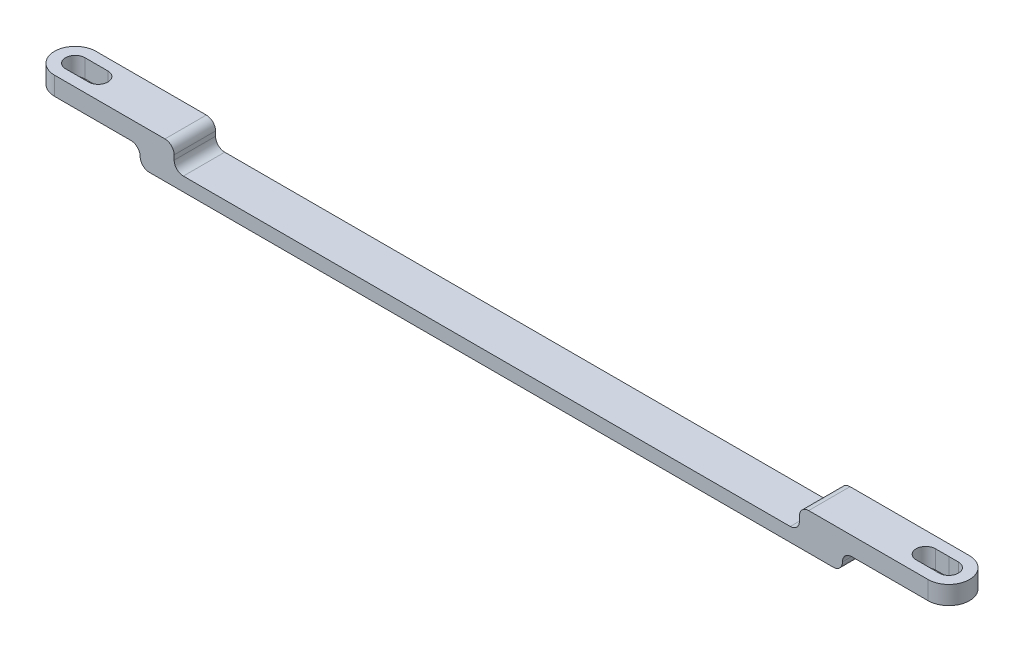
SolidWorks part; units mm, degrees
ref_plane "Front" through (0, 0, 0) normal (0, 0, 1) x (1, 0, 0)
ref_plane "Top" through (0, 0, 0) normal (0, 1, 0) x (1, 0, 0)
ref_plane "Right" through (0, 0, 0) normal (1, 0, 0) x (0, 0, -1)
sketch "Sketch1" plane through (0, 0, 0) normal (0, 1, 0) x (1, 0, 0)
  line L2 (180, 2.0983) -> (185, 2.0983)
  line L3 (180, -2.0983) -> (185, -2.0983)
  line L4 (-5, 2.1) -> (0, 2.1)
  line L5 (-5, -2.1) -> (0, -2.1)
  line L6 (2.8, 4.5) -> (177.1967, 4.5)
  line L11 (2.8, -4.5) -> (177.1967, -4.5)
  line L13 (177.1967, 4.5) -> (185, 4.5)
  line L14 (182.9258, 2.1078) -> (182.9176, 2.0983)
  line L15 (177.1967, -4.5) -> (185, -4.5)
  line L17 (2.8, -4.5) -> (-5, -4.5)
  line L19 (2.8, 4.5) -> (-5, 4.5)
  arc A0 (-5, 2.1) -> (-5, -2.1) centre (-5, 0) ccw
  arc A1 (0, -2.1) -> (0, 2.1) centre (0, 0) ccw
  arc A2 (185, -2.0983) -> (185, 2.0983) centre (185, 0) ccw
  arc A3 (180, 2.0983) -> (180, -2.0983) centre (180, 0) ccw
  arc A18 (182.9309, 2.0983) -> (182.9258, 2.1078) centre (178.95, 0) ccw
  arc A21 (185, -4.5) -> (185, 4.5) centre (185, 0) ccw
  arc A23 (-5, 4.5) -> (-5, -4.5) centre (-5, 0) ccw
  point P6 (178.95, 0)
extrude "Boss-Extrude1" add sketch "Sketch1" along normal blind 4 contours L19 A23 L17 L11 L15 A21 L13 L6 A1 L5 A0 L4 A18 L2 A2 L3 A3 L14 region at (90.0022, 0, 0)
sketch "Sketch2" plane through (0, 0, 0) normal (0, -1, 0) x (1, 0, 0)
  line L2 (13.6257, -4.5) -> (166.3743, -4.5)
  line L10 (13.6257, -4.5) -> (13.6257, 4.5)
  line L15 (166.3743, -4.5) -> (166.3743, 4.5)
  line L18 (13.6257, -4.5) -> (90, 0) construction
  line L19 (13.6257, 4.5) -> (166.3743, -4.5) construction
  line L20 (2.8, 4.5) -> (177.1967, 4.5) construction
  line L21 (166.3743, 4.5) -> (13.6257, 4.5)
  point P2 (90, 0)
extrude "Boss-Extrude2" add sketch "Sketch2" along normal blind 4
sketch "Sketch4" plane through (0, 4, 0) normal (0, 1, 0) x (1, 0, 0)
  line L0 (177.1967, 4.5) -> (2.8, 4.5) construction
  line L1 (21.0209, -4.5) -> (157.0209, -4.5)
  line L2 (21.0209, -4.5) -> (21.0209, 4.5)
  line L3 (21.0209, 4.5) -> (157.0209, 4.5)
  line L4 (157.0209, -4.5) -> (157.0209, 4.5)
  line L5 (21.0209, -4.5) -> (157.0209, 4.5) construction
  line L6 (21.0209, 4.5) -> (157.0209, -4.5) construction
  point P0 (89.0209, 0)
extrude "Cut-Extrude1" cut sketch "Sketch4" against normal blind 5
fillet "Fillet1" radius 2 8 edges at (157.0209, -1, 0) (13.6257, -4, 0) (21.0209, -1, 0) (166.3743, -4, 0) (21.0209, 4, 0) (13.6257, 0, 0) (166.3743, 0, 0) (157.0209, 4, 0)
